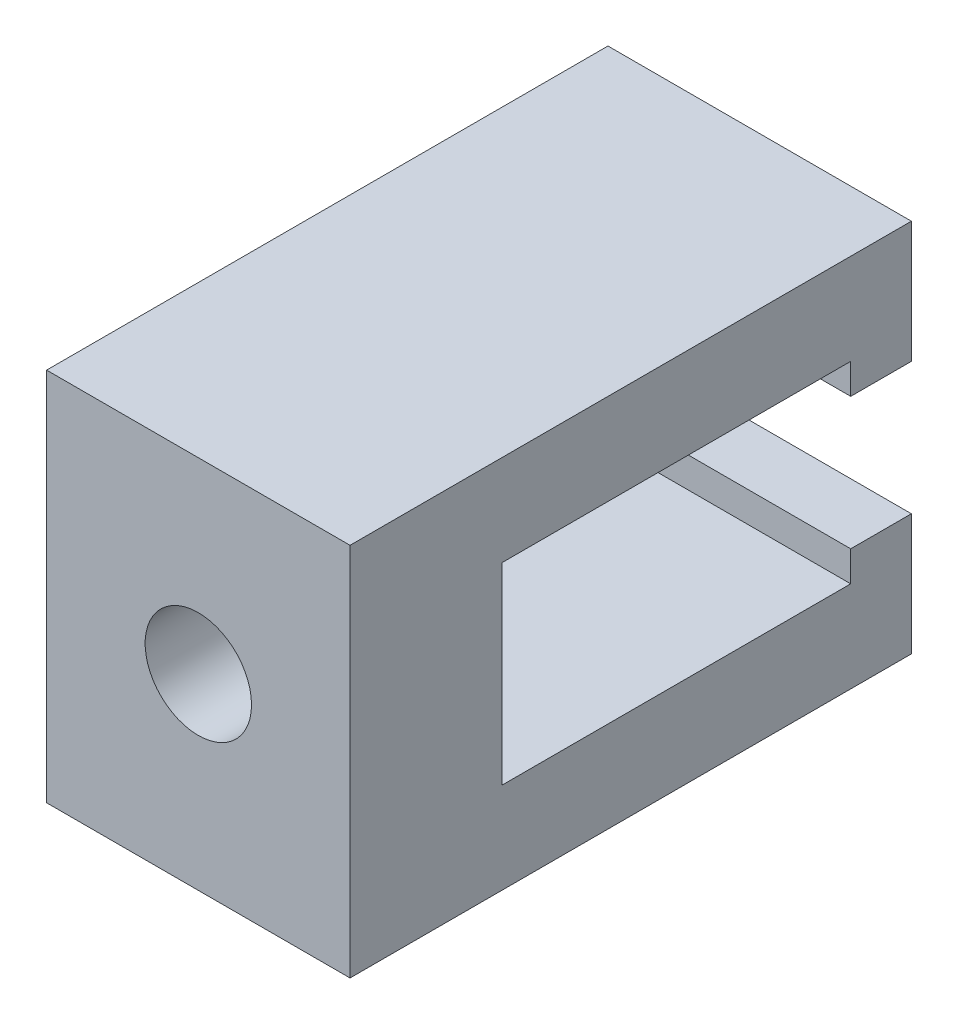
SolidWorks part; units mm, degrees
ref_plane "Front Plane" through (0, 0, 0) normal (0, 0, 1) x (1, 0, 0)
ref_plane "Top Plane" through (0, 0, 0) normal (0, 1, 0) x (1, 0, 0)
ref_plane "Right Plane" through (0, 0, 0) normal (1, 0, 0) x (0, 0, -1)
sketch "Sketch1" plane through (0, 0, 0) normal (1, 0, 0) x (0, 0, -1)
  line L5 (9.4948, 4.8363) -> (-9.0052, 4.8363)
  line L11 (-4.0052, -2.9262) -> (145.9948, -2.9262) construction
  line L12 (5.9948, 0.2488) -> (5.9948, -2.9262) construction
  line L15 (9.4948, 4.8363) -> (9.4948, 0.8363)
  line L16 (9.4948, 0.8363) -> (7.4948, 0.8363)
  line L17 (7.4948, 0.8363) -> (7.4948, 1.8363)
  line L18 (7.4948, 1.8363) -> (-4.0052, 1.8363)
  line L19 (-4.0052, 1.8363) -> (-4.0052, -4.5137)
  line L20 (-9.0052, 4.8363) -> (-9.0052, -7.5137)
  line L21 (7.4948, -4.5137) -> (-4.0052, -4.5137)
  line L22 (7.4948, -3.5137) -> (7.4948, -4.5137)
  line L23 (9.4948, -3.5137) -> (7.4948, -3.5137)
  line L25 (9.4948, -7.5137) -> (-9.0052, -7.5137)
  line L26 (9.4948, -3.5137) -> (9.4948, -7.5137)
  line L28 (-4.0052, 0.2488) -> (-4.0052, -2.9262) construction
  point P16 (-9.0052, -1.3387)
  point P17 (-4.0052, -1.3387)
  point P24 (-4.0052, -1.3387)
  dimension "D2" = 3
  dimension "D3" = 1
  dimension "D1" = 5
  dimension "D4" = 2
  dimension "D5" = 1.5
  dimension "D6" = 1.5875
extrude "MainBody" add sketch "Sketch1" along normal mid plane 10
hole_wizard "#6-32 Tapped Hole1" positions "Sketch2" profile "Sketch3" tap size "#6-32" standard "ANSI Inch" end condition through all
sketch "Sketch2" plane through (0, 0, 9.0052) normal (0, 0, 1) x (1, 0, 0)
  line L0 (5, 4.8363) -> (-5, 4.8363) construction
  line L1 (-5, 4.8363) -> (-5, -7.5137) construction
  point P0 (0, -1.3387)
  point P4 (0, 4.8363)
  point P7 (-5, -1.3387)
sketch "Sketch3" plane through (0, -1.3387, 9.0052) normal (1, 0, 0) x (0, -1, 0)
  line L0 (0, 0) -> (0, 18.5)
  line L1 (0, 18.5) -> (1.7526, 18.5)
  line L2 (1.7526, 18.5) -> (1.7526, 0)
  line L5 (1.7526, 0) -> (0, 0)
  line L11 (0, -6.35) -> (0, 107.95) construction
  dimension "Thread Major Dia." = 3.5052
  dimension "Thru Tap Drill Depth" = 18.5
equation "\"HeightBarThickness\"= 1.5875"
equation "\"HeightBarWidth\"=6"
equation "\"SheetThickness\" = 1.5875"
equation "\"D2@Sketch1\"=3mm"
equation "\"HeightBarTolerance\"= 0.1mm"
